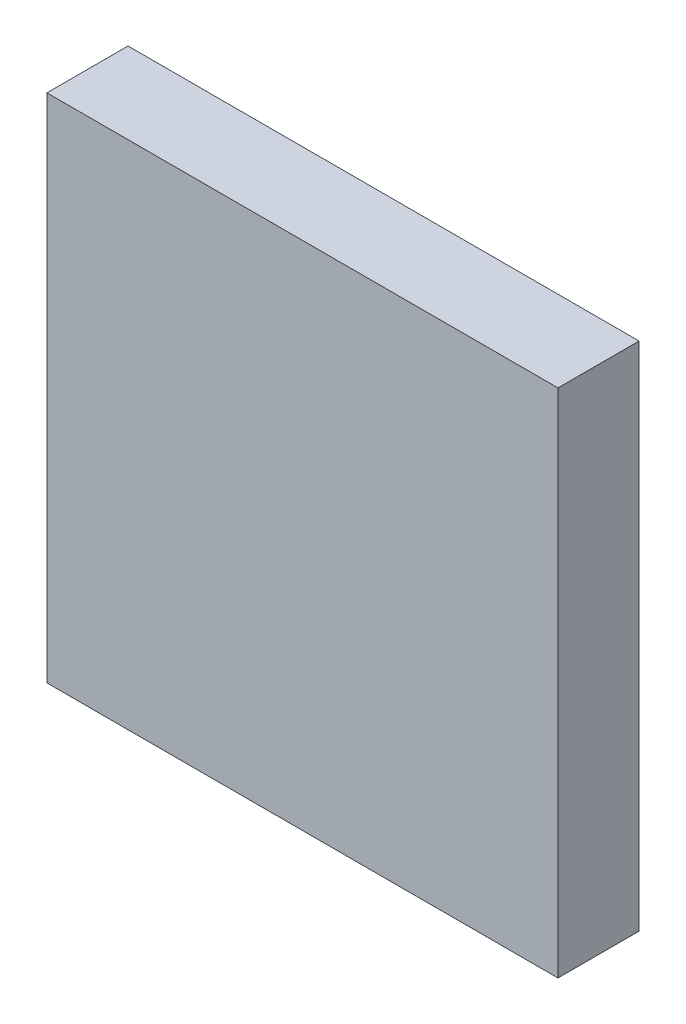
SolidWorks part; units mm, degrees
ref_plane "Front Plane" through (0, 0, 0) normal (0, 0, 1) x (1, 0, 0)
ref_plane "Top Plane" through (0, 0, 0) normal (0, 1, 0) x (1, 0, 0)
ref_plane "Right Plane" through (0, 0, 0) normal (1, 0, 0) x (0, 0, -1)
sketch "Sketch1" plane through (0, 0, 0) normal (0, 0, 1) x (1, 0, 0)
  line L1 (0, 0) -> (20, 0)
  line L2 (0, 0) -> (0, 20)
  line L3 (0, 20) -> (20, 20)
  line L4 (20, 0) -> (20, 20)
extrude "Boss-Extrude1" add sketch "Sketch1" along normal blind 3.175
